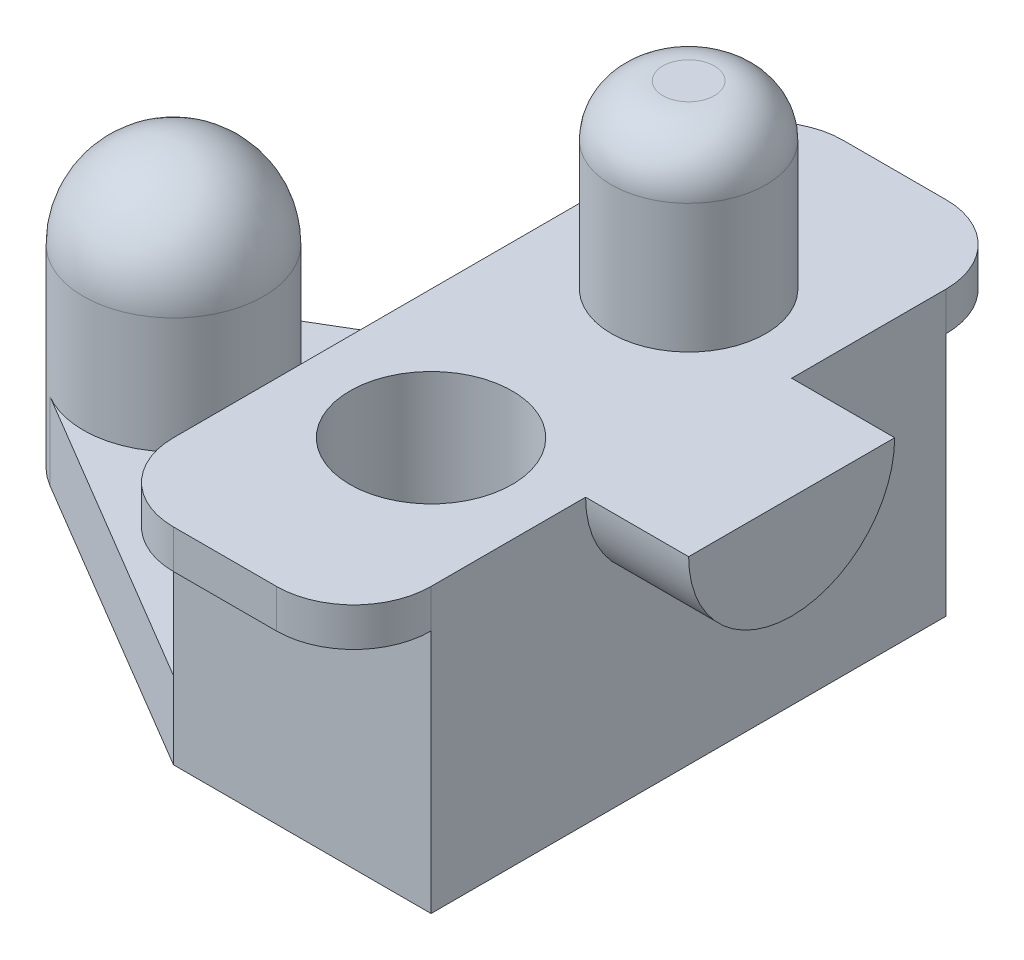
SolidWorks part; units mm, degrees
other "Markup1"
sketch "Sketch7" plane through (12, 7.5, 6.5) normal (0.0383, 0.9456, 0.3232) x (0.9932, -0.0006, -0.1161)
ref_plane "Front Plane" through (0, 0, 0) normal (0, 0, 1) x (1, 0, 0)
ref_plane "Top Plane" through (0, 0, 0) normal (0, 1, 0) x (1, 0, 0)
ref_plane "Right Plane" through (0, 0, 0) normal (1, 0, 0) x (0, 0, -1)
sketch "Sketch1" plane through (0, 0, 0) normal (0, 1, 0) x (1, 0, 0)
  line L0 (5, 5) -> (10, 5)
  line L1 (10, 5) -> (10, -5)
  line L2 (10, -5) -> (5, -5)
  line L3 (5, -5) -> (-0.8927, -1.5052)
  line L4 (5, 5) -> (-0.8927, 1.5052)
  arc A0 (-0.8927, 1.5052) -> (-0.8927, -1.5052) centre (0, 0) ccw
  point P7 (-7.8486, -3.1285)
  point P8 (0, 0)
  point P11 (10, 0)
  point P13 (10, -5)
  dimension "D1" = 10
  dimension "D4" = 5
  dimension "D5" = 1.75
  dimension "D2" = 5
  dimension "D3" = 5
extrude "Boss-Extrude1" add sketch "Sketch1" against normal blind 1.5 contours L1 L2 L3 A0 L4 L0
sketch "Sketch2" plane through (0, 0, 0) normal (0, 1, 0) x (1, 0, 0)
  line L1 (5, 5) -> (10, 5)
  line L2 (5, 5) -> (5, -5)
  line L3 (5, -5) -> (10, -5)
  line L4 (10, 5) -> (10, -5)
  circle A0 centre (0, 0) radius 1.75
  dimension "D1" = 3.5
extrude "Boss-Extrude2" add sketch "Sketch2" along normal blind 4
sketch "Sketch3" plane through (0, 4, 0) normal (0, 1, 0) x (1, 0, 0)
  line L0 (5, 5) -> (10, 5)
  line L1 (6.5, 6.5) -> (8.5, 6.5)
  line L2 (10, -5) -> (10, 5) construction
  line L3 (5, 5) -> (5, -5) construction
  line L4 (-0.825, 0) -> (0.825, 0) construction
  line L5 (6.5, -6.5) -> (8.5, -6.5)
  line L6 (5, -5) -> (10, -5)
  arc A0 (8.5, 6.5) -> (10, 5) centre (8.5, 5) cw
  arc A1 (6.5, 6.5) -> (5, 5) centre (6.5, 5) ccw
  arc A2 (6.5, -6.5) -> (5, -5) centre (6.5, -5) cw
  arc A3 (8.5, -6.5) -> (10, -5) centre (8.5, -5) ccw
  point P8 (5.9878, 6.1734)
  point P9 (5.9914, 6.5)
  dimension "D2" = 1.5
extrude "Boss-Extrude3" add sketch "Sketch3" against normal blind 0.75
fillet "Fillet1" radius 1.75 1 edges at (0, 4, 1.75)
sketch "Sketch4" plane through (0, 4, 0) normal (0, 1, 0) x (1, 0, 0)
  line L0 (5, 5) -> (5, -5) construction
  circle A0 centre (7.5, 2.5) radius 1.5
  point P2 (7.6142, 2.3865)
  dimension "D1" = 3
  dimension "D2" = 2.5
  dimension "D3" = 2.5
extrude "Boss-Extrude4" add sketch "Sketch4" along normal blind 3.5
fillet "Fillet2" radius 1 1 edges at (7.5, 7.5, -1)
sketch "Sketch5" plane through (0, 4, 0) normal (0, 1, 0) x (1, 0, 0)
  line L0 (5, 5) -> (5, -5) construction
  circle A0 centre (7.5, -2.5) radius 1.575
  dimension "D1" = 3.15
  dimension "D2" = 2.5
  dimension "D3" = 2.5
extrude "Cut-Extrude1" cut sketch "Sketch5" against normal blind 3.75
sketch "Sketch6" plane through (10, 0, 0) normal (1, 0, 0) x (0, 0, -1)
  line L0 (-5, 4) -> (5, 4) construction
  line L1 (-2, 4) -> (2, 4)
  arc A0 (-2, 4) -> (2, 4) centre (0, 4) ccw
  dimension "D1" = 4
extrude "Boss-Extrude5" add sketch "Sketch6" along normal blind 2
